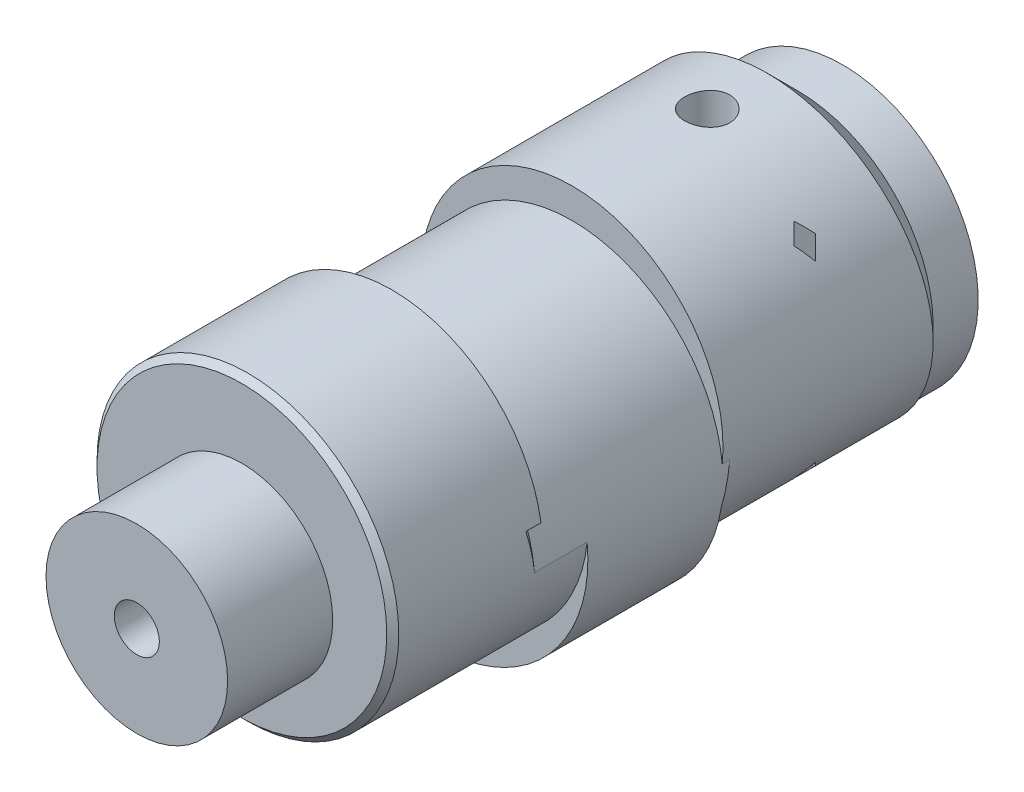
SolidWorks part; units mm, degrees
ref_plane "Front Plane" through (0, 0, 0) normal (0, 0, 1) x (1, 0, 0)
ref_plane "Top Plane" through (0, 0, 0) normal (0, 1, 0) x (1, 0, 0)
ref_plane "Right Plane" through (0, 0, 0) normal (1, 0, 0) x (0, 0, -1)
ref_plane "Plane1"
sketch "Sketch1" plane through (0, 0, 0) normal (0, 0, 1) x (1, 0, 0)
  circle A0 centre (0, 1) radius 10.05
  circle A1 centre (0, 0) radius 1.5
  dimension "D1" = 3
  dimension "D2" = 20.1
extrude "Extrusion1" add sketch "Sketch1" along normal blind 18 contours A0 A1
ref_plane "Plane2" through (0, 1, 18) normal (0, 0, 1) x (1, 0, 0)
sketch "Sketch2" plane through (0, 1, 18) normal (0, 0, 1) x (1, 0, 0)
  circle A0 centre (0, -2) radius 10.05
  circle A1 centre (0, -1) radius 1.5
  dimension "D1" = 1
extrude "Extrusion2" add sketch "Sketch2" along normal blind 13 contours A0 A1
ref_plane "Plane3" through (0, -1, 31) normal (0, 0, 1) x (1, 0, 0)
sketch "Sketch3" plane through (0, -1, 31) normal (0, 0, 1) x (1, 0, 0)
  circle A0 centre (0, 2) radius 10.05
  circle A1 centre (0, 1) radius 1.5
  dimension "D1" = 1
extrude "Extrusion3" add sketch "Sketch3" along normal blind 9 contours A0 A1
ref_plane "Plane4" through (0, 1, 31) normal (0, 0, 1) x (1, 0, 0)
sketch "Sketch4" plane through (0, 1, 31) normal (0, 0, 1) x (1, 0, 0)
  arc A0 (-10.0001, -1) -> (10.0001, -1) centre (0, -2) ccw
  arc A1 (-10.0001, -1) -> (10.0001, -1) centre (0, 0) ccw
extrude "Extrusion4" cut sketch "Sketch4" against normal blind 4
ref_plane "Plane5" through (0, 1, 40) normal (0, 0, 1) x (1, 0, 0)
sketch "Sketch5" plane through (0, 1, 40) normal (0, 0, 1) x (1, 0, 0)
  circle A0 centre (0, -1) radius 6.05
  circle A1 centre (0, -1) radius 1.5
  dimension "D1" = 12.1
extrude "Extrusion5" add sketch "Sketch5" along normal blind 7 contours A0 A1
ref_plane "Plane6" through (0, 1, 0) normal (0, 0, -1) x (-1, 0, 0)
sketch "Sketch6" plane through (0, 1, 0) normal (0, 0, -1) x (-1, 0, 0)
  circle A0 centre (0, -1) radius 3.175
  circle A1 centre (0, -1) radius 1.5
  dimension "D1" = 6.35
extrude "Extrusion6" cut sketch "Sketch6" against normal blind 22 contours A0 A1
ref_plane "Plane7" through (0, 0, 0) normal (0, 1, 0) x (-1, 0, 0)
sketch "Sketch7" plane through (0, 0, 0) normal (0, 1, 0) x (-1, 0, 0)
  line L0 (-2.75, 7.4123) -> (-2.75, 10.5877)
  line L1 (-2.75, 10.5877) -> (0, 12.1754)
  line L2 (0, 12.1754) -> (2.75, 10.5877)
  line L3 (2.75, 10.5877) -> (2.75, 7.4123)
  line L4 (2.75, 7.4123) -> (0, 5.8246)
  line L5 (0, 5.8246) -> (-2.75, 7.4123)
  dimension "D1" = 5.5
extrude "Extrusion7" cut sketch "Sketch7" along normal blind 4.5
ref_plane "Plane8" through (0, 0, 9) normal (0, -1, 0) x (0, 0, -1)
hole_wizard "Hole2" positions "Sketch9" profile "Sketch8" legacy
sketch "Sketch9" plane through (0, 0, 9) normal (0, -1, 0) x (0, 0, -1)
  point P1 (0, 0)
sketch "Sketch8" plane through (0, 0, 9) normal (1, 0, 0) x (0, 0, -1)
  line L0 (0, 0) -> (0, 11.05)
  line L1 (0, 11.05) -> (1.5, 11.05)
  line L2 (1.5, 11.05) -> (1.5, 0)
  line L3 (1.5, 0) -> (0, 0)
  line L4 (0, 110) -> (0, -10) construction
  dimension "Diameter" = 3
  dimension "Depth" = 11.05
ref_plane "Plane9" through (0, 0, 0) normal (0, 1, 0) x (-1, 0, 0)
sketch "Sketch10" plane through (0, 0, 0) normal (0, 1, 0) x (-1, 0, 0)
  line L0 (-7.5, 9.2929) -> (-6.7929, 10)
  line L1 (-6.7929, 10) -> (-7.5, 10.7071)
  line L2 (-7.5, 10.7071) -> (-8.2071, 10)
  line L3 (-8.2071, 10) -> (-7.5, 9.2929)
  line L4 (7.5, 9.2929) -> (8.2071, 10)
  line L5 (8.2071, 10) -> (7.5, 10.7071)
  line L6 (7.5, 10.7071) -> (6.7929, 10)
  line L7 (6.7929, 10) -> (7.5, 9.2929)
  dimension "D1" = 1
  dimension "D2" = 1
extrude "Extrusion8" cut sketch "Sketch10" against normal through all and the other way through all contours L2 L3 L0 L1 | L6 L7 L4 L5
chamfer "Chamfer1" distance 0.4 distance2 0.4 1 edges at (10.05, 1, 40)
ref_plane "Plane10" through (0, 1, 40) normal (0, 0, 1) x (1, 0, 0)
sketch "Sketch11" plane through (0, 1, 40) normal (0, 0, 1) x (1, 0, 0)
  circle A0 centre (0, -1) radius 7.55
  circle A1 centre (0, -1) radius 6.05
ref_plane "Plane11" through (0, 0, 0) normal (1, 0, 0) x (0, 1, 0)
sketch "Sketch12" plane through (0, 0, 0) normal (1, 0, 0) x (0, 1, 0)
  line L0 (-9.05, 0) -> (-9.05, 3)
  line L1 (-9.05, 3) -> (-13.05, 3)
  line L2 (-13.05, 3) -> (-13.05, 0)
  line L3 (-13.05, 0) -> (-9.05, 0)
  line L4 (0, -4.4) -> (0, 26.4) construction
  line L5 (-9.05, 3) -> (-13.05, 7)
  line L6 (-13.05, 7) -> (-13.05, 3)
  line L7 (-13.05, 3) -> (-9.05, 3)
  point P7 (0, 0)
  dimension "D1" = 4
  dimension "D2" = 4
  dimension "D3" = 3
revolve "Revolution1" cut sketch "Sketch12" angle 360 about L4
chamfer "Chamfer2" distance 1.6 distance2 1.6 1 edges at (-1.5, 0, 22)
chamfer "Chamfer3" distance 0.5 distance2 0.5 1 edges at (0, 9.05, 31)
chamfer "Chamfer4" distance 0.5 distance2 0.5 1 edges at (0, -9.05, 18)
ref_plane "Plane12" through (0, -1, 31) normal (0, 0, -1) x (-1, 0, 0)
sketch "Sketch13" plane through (0, -1, 31) normal (0, 0, -1) x (-1, 0, 0)
  arc A0 (9.9258, 3.575) -> (-9.9258, 3.575) centre (0, 2) ccw
  arc A1 (9.9258, 3.575) -> (-9.9258, 3.575) centre (0, 0) ccw
extrude "Extrusion10" add sketch "Sketch13" along normal blind 1
